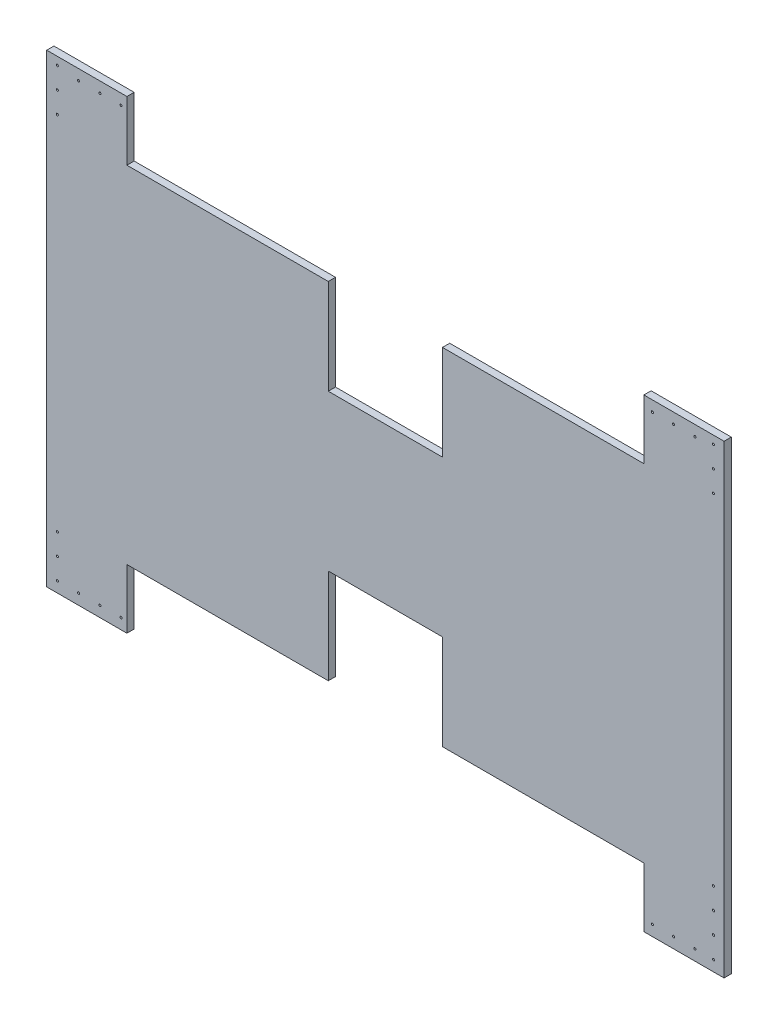
SolidWorks part; units mm, degrees
ref_plane "Front Plane" through (0, 0, 0) normal (0, 0, 1) x (1, 0, 0)
ref_plane "Top Plane" through (0, 0, 0) normal (0, 1, 0) x (1, 0, 0)
ref_plane "Right Plane" through (0, 0, 0) normal (1, 0, 0) x (0, 0, -1)
sketch "Sketch1" plane through (0, 0, 0) normal (0, 0, 1) x (1, 0, 0)
  line L1 (-301.3367, -246.0625) -> (-301.3367, -252.4125) construction
  line L2 (-259.1585, -213.0298) -> (-269.5788, -213.0298) construction
  line L3 (301.3367, -252.4125) -> (301.3367, -246.0625) construction
  line L4 (-404.8125, -277.8125) -> (-404.8125, 277.8125)
  line L5 (404.8125, -277.8125) -> (404.8125, 277.8125)
  line L6 (404.8125, 277.8125) -> (-404.8125, 277.8125)
  line L7 (404.8125, -277.8125) -> (-404.8125, -277.8125)
  line L8 (-404.8125, 0) -> (404.8125, 0) construction
  line L9 (308.9567, -277.8125) -> (68.2625, -277.8125)
  line L10 (308.9567, -277.8125) -> (308.9567, -206.6862)
  line L11 (308.9567, -206.6862) -> (67.1811, -206.6862)
  line L13 (68.2625, -277.8125) -> (-68.2625, -277.8125)
  line L14 (68.2625, -277.8125) -> (68.2625, -93.0519)
  line L15 (68.2625, -93.0519) -> (-68.2625, -93.0519)
  line L16 (-68.2625, -277.8125) -> (-68.2625, -93.0519)
  line L17 (-68.2625, -277.8125) -> (-308.9567, -277.8125)
  line L19 (-68.2625, -206.6798) -> (-308.9567, -206.6798)
  line L20 (-308.9567, -277.8125) -> (-308.9567, -206.6798)
  line L22 (278.8865, -223.7042) -> (254.5025, -223.7042) construction
  line L24 (67.1811, -206.6862) -> (68.2625, -206.6862)
  circle A6 centre (319.0875, 265.1125) radius 1.27
  circle A7 centre (344.4875, 265.1125) radius 1.27
  circle A8 centre (369.8875, 265.1125) radius 1.27
  circle A9 centre (392.1125, 217.4875) radius 1.27
  circle A10 centre (392.1125, 242.8875) radius 1.27
  circle A11 centre (392.1125, 268.2875) radius 1.27
  circle A12 centre (-315.9125, -265.1125) radius 1.27
  circle A13 centre (-341.3125, -265.1125) radius 1.27
  circle A14 centre (-366.7125, -265.1125) radius 1.27
  circle A15 centre (-392.1125, -214.3125) radius 1.27
  circle A16 centre (-392.1125, -239.7125) radius 1.27
  circle A17 centre (-392.1125, -265.1125) radius 1.27
  circle A18 centre (-315.9125, 265.1125) radius 1.27
  circle A19 centre (-341.3125, 265.1125) radius 1.27
  circle A20 centre (-366.7125, 265.1125) radius 1.27
  circle A21 centre (-392.1125, 217.4875) radius 1.27
  circle A22 centre (-392.1125, 242.8875) radius 1.27
  circle A23 centre (-392.1125, 268.2875) radius 1.27
  circle A31 centre (319.0875, -265.1125) radius 1.27
  circle A32 centre (392.1125, -188.9125) radius 1.27
  circle A33 centre (392.1125, -214.3125) radius 1.27
  circle A34 centre (392.1125, -239.7125) radius 1.27
  circle A35 centre (392.1125, -265.1125) radius 1.27
  circle A36 centre (369.8875, -265.1125) radius 1.27
  circle A37 centre (344.4875, -265.1125) radius 1.27
  dimension "D1" = 277.8125
  dimension "D2" = 555.625
  dimension "D3" = 404.8125
  dimension "D4" = 809.625
  dimension "D5" = 336.55
  dimension "D6" = 7.62
  dimension "D7" = 6.35
  dimension "D8" = 7.62
  dimension "D9" = 336.55
  dimension "D10" = 17.018
extrude "Boss-Extrude1" add sketch "Sketch1" along normal mid plane 8.636 contours L8 L4 L7 L20 L19 L16 L15 L14 L11 L10 L5 A37 A36 A35 A34 A33 A32 A31 A17 A16 A15 A14 A13 | L4 L8 L5 L6 A18 A19 A20 A21 A22 A23 | L16 L7 L14 L15 | L7 L10 L11 | L20 L7 L19 A12 region at (-396.2529, -138.9062, 0) region at (-0.0002, 138.8751, 0) region at (-188.6096, -242.2461, 0) region at (0, -185.4322, 0) region at (188.6096, -242.2493, 0)
extrude "Cut-Extrude2" cut sketch "Sketch1<3>" along normal through all both and the other way through all contours L7 L10 L11 | L16 L7 L14 L15 | L20 L7 L19 A12 region at (-188.6096, -242.2461, 0) region at (0, -185.4322, 0) region at (188.6096, -242.2493, 0)
sketch "Sketch1<3>" plane through (0, 0, 0) normal (0, 0, 1) x (1, 0, 0) same geometry as "Sketch1"
mirror "Mirror1" about plane through (0, 0, 0) normal (0, 1, 0) of "Cut-Extrude2"
